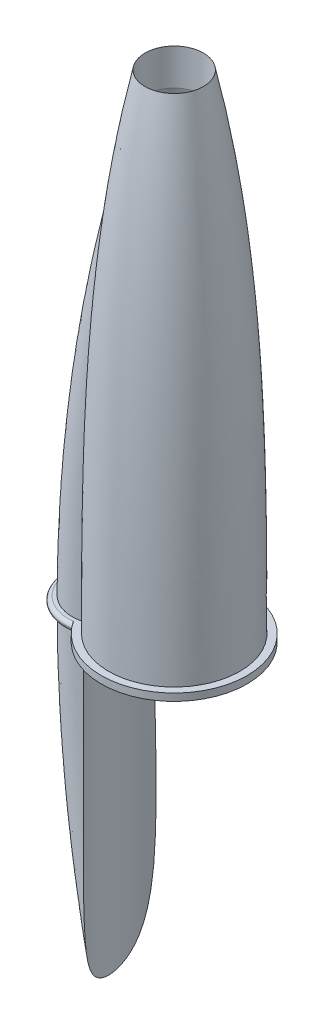
SolidWorks part; units mm, degrees
ref_plane "Alzado" through (0, 0, 0) normal (0, 0, 1) x (1, 0, 0)
ref_plane "Planta" through (0, 0, 0) normal (0, 1, 0) x (1, 0, 0)
ref_plane "Vista lateral" through (0, 0, 0) normal (1, 0, 0) x (0, 0, -1)
sketch "Croquis1" plane through (0, 0, 0) normal (0, 0, 1) x (1, 0, 0)
  line L0 (0, 0) -> (0, 37.6987) construction
  line L1 (4, 0) -> (5, 0)
  line L2 (5, 0) -> (5, 34) construction
  line L3 (5, 34) -> (0, 34) construction
  line L4 (5, 0) -> (5, 0.5)
  line L5 (5, 0.5) -> (4.5, 0.5)
  line L6 (0, 34) -> (2, 34)
  line L7 (4, 0.5) -> (4, 0)
  line L8 (2, 34) -> (2, 31.5013)
  line L9 (4, 0) -> (0, 0)
  line L10 (0, 0) -> (0, 34)
  line L11 (0, 34) -> (-0.0201, 33.9688)
  spline S0 degree 3 poles (2, 34) (4.4043, 23.0634) (4.5, 11.7004) (4.5, 0.5) knots 0 0 0 0 1 1 1 1
  spline S2 degree 3 poles (2, 31.5013) (2.883, 26.8308) (3.9547, 16.5379) (4, 6.1079) (4, 0.5) knots 0.073058 0.073058 0.073058 0.073058 0.5 1 1 1 1
  dimension "D1" = 34
  dimension "D2" = 5
  dimension "D3" = 0.5
  dimension "D4" = 0.5
  dimension "D5" = 2
revolve "Revolución1" add sketch "Croquis1" angle 360 about L0 region at (4.3413, 0.25, 0)
sketch "Croquis2" plane through (0, 0, 0) normal (0, 0, 1) x (1, 0, 0)
  line L0 (-5, 0) -> (-7, 0) construction
  spline S0 degree 2 poles (-7, 0) (-7, 13.6304) (-3.2379, 27) knots 0 0 0 1 1 1
  spline S1 degree 3 poles (-2, 34) (-4.4043, 23.0634) (-4.5, 11.7004) (-4.5, 0.5) knots 0 0 0 0 1 1 1 1 construction
  dimension "D1" = 2
  dimension "D2" = 27
sketch "Croquis3" plane through (0, 0, 0) normal (0, 1, 0) x (1, 0, 0)
  line L0 (-5, 0) -> (-7, 0) construction
  circle A0 centre (-4.5, 0) radius 2.5
  dimension "D1" = 5
sweep "Barrer2" add profiles "Croquis3" path "Croquis2"
revolve "Cortar-Revolución4" cut sketch "Croquis1<5>" angle 360 about L10 region at (1.7574, 15.1904, 0)
sketch "Croquis1<5>" plane through (0, 0, 0) normal (0, 0, 1) x (1, 0, 0) same geometry as "Croquis1"
mirror "Simetría1" about plane through (0, 0, 0) normal (0, -1, 0) of "Barrer2"
sketch "Croquis5" plane through (0, 0, 0) normal (0, -1, 0) x (1, 0, 0)
  circle A0 centre (0, 0) radius 4.5
extrude "Cortar-Extruir1" cut sketch "Croquis5" along normal through all
chamfer "Chaflán1" distance 0.5 angle 45 1 edges at (0, 0, -4)
sketch "Croquis6" plane through (0, 0, 0) normal (0, 1, 0) x (1, 0, 0)
  circle A0 centre (0, 0) radius 5
  arc A2 (-4.0278, 2.9626) -> (-4.0278, -2.9626) centre (-4.5, 0) ccw
  dimension "D1" = 6
extrude "Saliente-Extruir1" add sketch "Croquis6" along normal blind 0.5 contours A0 A2 region at (-5.8537, 0, 0)
fillet "Redondeo1" radius 0.25 2 edges at (-7.5, 0, 0) (-7.5, 0.5, 0)
ref_axis "Eje1" through (0, -22.578, 0) along (0, 1, 0)
